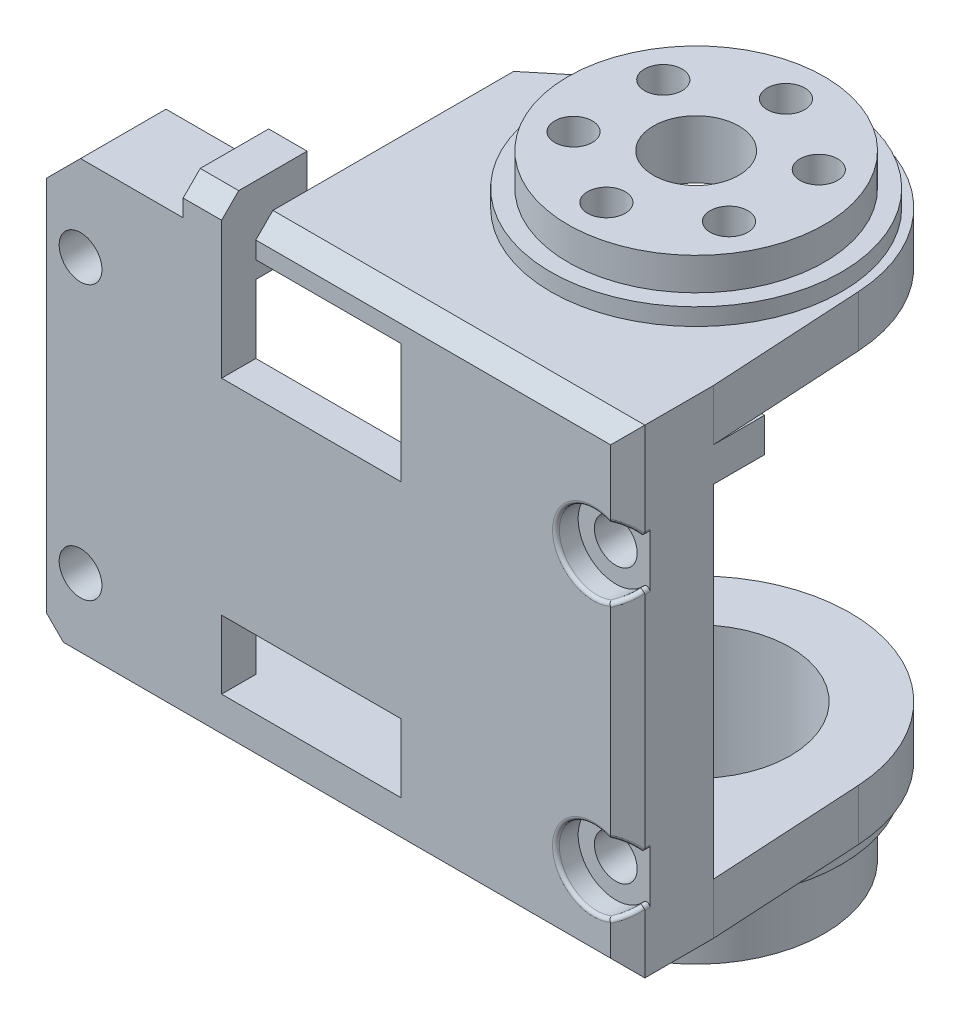
SolidWorks part; units mm, degrees
ref_plane "前视基准面" through (0, 0, 0) normal (0, 0, 1) x (1, 0, 0)
ref_plane "上视基准面" through (0, 0, 0) normal (0, 1, 0) x (1, 0, 0)
ref_plane "右视基准面" through (0, 0, 0) normal (1, 0, 0) x (0, 0, -1)
sketch "草图1" plane through (0, 0, 0) normal (0, 0, 1) x (1, 0, 0)
  line L0 (-26, 14) -> (-26, 12)
  line L1 (0, 14) -> (-34, 14)
  line L2 (0, 14) -> (0, -14)
  line L3 (0, -14) -> (-34, -14)
  line L4 (-34, 14) -> (-34, -14)
  line L5 (-26, 12) -> (-34, 12)
  dimension "D1" = 28
  dimension "D2" = 34
  dimension "D3" = 2
  dimension "D4" = 8
extrude "凸台-拉伸1" add sketch "草图1" against normal blind 2 contours L0 L5 L4 L3 L2 L1 | L5 L0 L1 L4 region at (-16.7778, -0.2222, 0) region at (-30, 13, 0)
sketch "草图2" plane through (0, -14, 0) normal (0, -1, 0) x (1, 0, 0)
  line L0 (-34, 0) -> (-34, -5)
  line L1 (0, 0) -> (-34, 0) construction
  line L2 (-34, 0) -> (0, 0)
  line L3 (0, -2) -> (0, 0) construction
  line L4 (0, 0) -> (0, -5)
  line L5 (-15.2175, -20.4505) -> (-34, -5)
  line L6 (0, -5) -> (-0.5146, -14.0131)
  circle A0 centre (-9.5, -13.5) radius 9
  line M7 (0, 0) -> (-34, 0)
  line M8 (-34, 0) -> (-34, -2)
  line M9 (-34, -2) -> (0, -2)
  line M10 (0, -2) -> (0, 0)
  dimension "D2" = 9.5
  dimension "D3" = 18
  dimension "D1" = 13.5
  dimension "D4" = 5
  dimension "D5" = 5
  dimension "D6" = 34
extrude "凸台-拉伸2" add sketch "草图2" against normal blind 3 contours M10 M7 M8 M9 | A0 L6 L4 L0 L5 M9 | A0 region at (-17, -14, -1) region at (-18.8639, -14, -6.5539) region at (-9.5, -14, -13.5)
ref_axis "基准轴1" through (-9.5, -11, -13.5) along (0, -1, 0)
sketch "草图4" plane through (0, -14, 0) normal (0, -1, 0) x (1, 0, 0)
  circle A0 centre (-9.5, -13.5) radius 7.5
  dimension "D1" = 15
extrude "凸台-拉伸3" add sketch "草图4" along normal blind 5
sketch "草图5" plane through (0, -14, 0) normal (0, -1, 0) x (1, 0, 0)
  circle A2 centre (-9.5, -13.5) radius 8.5
  circle A3 centre (-9.5, -13.5) radius 8.5
  dimension "D1" = 1
extrude "凸台-拉伸4" add sketch "草图5" along normal blind 1
mirror "镜向1" about plane through (0, 0, 0) normal (0, 1, 0) of "凸台-拉伸2", "凸台-拉伸4", "凸台-拉伸3"
sketch "草图6" plane through (0, 19, 0) normal (0, 1, 0) x (1, 0, 0)
  circle A1 centre (-9.5, 13.5) radius 7.5
  circle A2 centre (-9.5, 13.5) radius 7.5
  dimension "D1" = 0
extrude "切除-拉伸1" cut sketch "草图6" against normal blind 2.1
sketch "草图7" plane through (0, 0, -2) normal (0, 0, -1) x (-1, 0, 0)
  line L0 (15.2175, -11) -> (34, -11) construction
  line L1 (13.25, -7) -> (23.75, -7)
  line L2 (13.25, -7) -> (13.25, -11)
  line L3 (13.25, -11) -> (23.75, -11)
  line L4 (23.75, -7) -> (23.75, -11)
  line L5 (34, 11) -> (34, -11) construction
  line L7 (13.25, 12) -> (21.75, 12)
  line L8 (13.25, 12) -> (13.25, 5)
  line L9 (13.25, 5) -> (23.75, 5)
  line L11 (0, 14) -> (34, 14) construction
  line L14 (23.75, 14) -> (21.75, 14)
  line L15 (21.75, 12) -> (21.75, 14)
  line L16 (23.75, 14) -> (23.75, 5)
  dimension "D1" = 10.25
  dimension "D2" = 10.5
  dimension "D3" = 4
  dimension "D4" = 12
  dimension "D5" = 2
  dimension "D6" = 7
extrude "切除-拉伸2" cut sketch "草图7" against normal through all and the other way through all
sketch "草图8" plane through (0, 0, -2) normal (0, 0, -1) x (-1, 0, 0)
  line L0 (0, 11) -> (13.25, 11) construction
  line L1 (0, 11) -> (1.26, 11)
  line L2 (0, 11) -> (0, 9)
  line L3 (0, 9) -> (1.26, 9)
  line L4 (1.26, 11) -> (1.26, 9)
  line L5 (11.99, 11) -> (13.25, 11)
  line L6 (11.99, 11) -> (11.99, 9)
  line L7 (11.99, 9) -> (13.25, 9)
  line L8 (13.25, 11) -> (13.25, 9)
  line L9 (13.25, 5) -> (13.25, 11) construction
  dimension "D1" = 1.26
  dimension "D2" = 2
extrude "凸台-拉伸5" add sketch "草图8" along normal blind 3
sketch "草图9" plane through (0, 0, -5) normal (0, 0, -1) x (-1, 0, 0)
  line L0 (34, 11) -> (34, -11) construction
  line L1 (23.75, 11) -> (34, 11)
  line L2 (23.75, 11) -> (23.75, 9)
  line L3 (23.75, 9) -> (34, 9)
  line L4 (34, 11) -> (34, 9)
  line L5 (13.25, 9) -> (13.25, 11) construction
extrude "凸台-拉伸6" add sketch "草图9" against normal up to surface (3 mm away) up to face at (-15.1562, 2, -2)
sketch "草图10" plane through (0, 0, -5) normal (0, 0, -1) x (-1, 0, 0)
  line L1 (23.75, 9) -> (34, 9)
  line L2 (23.75, 9) -> (23.75, 14)
  line L3 (23.75, 14) -> (34, 14)
  line L4 (34, 9) -> (34, 14)
extrude "切除-拉伸3" cut sketch "草图10" along normal through all
sketch "草图11" plane through (0, 0, -5) normal (0, 0, -1) x (-1, 0, 0)
  line L1 (34, 14) -> (26, 14)
  line L2 (34, 14) -> (34, 12)
  line L3 (34, 12) -> (26, 12)
  line L4 (26, 14) -> (26, 12)
  point P5 (0, 0)
  dimension "D1" = 2
  dimension "D2" = 8
extrude "切除-拉伸4" cut sketch "草图11" against normal through all
sketch "草图21" plane through (0, 0, -5) normal (0, 0, -1) x (-1, 0, 0)
  line L0 (11.99, 11) -> (11.99, 9) construction
  line L1 (11.99, 9) -> (13.25, 9) construction
  line L2 (13.25, 9) -> (13.25, 11) construction
  line L3 (13.25, 11) -> (11.99, 11) construction
  line L4 (0, 11) -> (0, 9) construction
  line L5 (0, 9) -> (1.26, 9) construction
  line L6 (1.26, 9) -> (1.26, 11) construction
  line L7 (1.26, 11) -> (0, 11) construction
  line L8 (11.99, 11) -> (11.99, 9)
  line L9 (11.99, 9) -> (13.25, 9)
  line L10 (13.25, 9) -> (13.25, 11)
  line L11 (13.25, 11) -> (11.99, 11)
  line L12 (0, 11) -> (0, 9)
  line L13 (0, 9) -> (1.26, 9)
  line L14 (1.26, 9) -> (1.26, 11)
  line L15 (1.26, 11) -> (0, 11)
extrude "凸台-拉伸7" add sketch "草图21" along normal blind 3
sketch "草图20" plane through (0, 0, -2) normal (0, 0, -1) x (-1, 0, 0)
  line L0 (9.5, 6) -> (13.25, 6)
  line L1 (0, 0) -> (9.5, 0) construction
  line L2 (9.5, 0) -> (9.5, -1) construction
  line L3 (9.5, -8) -> (13.25, -8)
  line L4 (13.25, -8) -> (13.25, -11)
  line L5 (13.25, -11) -> (0, -11)
  line L6 (0, -11) -> (0, 11)
  line L7 (0, 11) -> (13.25, 11)
  line L8 (13.25, 11) -> (13.25, 6)
  line L9 (1.26, 11) -> (11.99, 11) construction
  line L10 (13.25, 5) -> (13.25, 9) construction
  arc A0 (9.5, 6) -> (9.5, -8) centre (9.5, -1) ccw
  arc A2 (9.5, -8) -> (9.5, 6) centre (9.5, -1) ccw construction
  dimension "D1" = 14
  dimension "D2" = 9.5
  dimension "D3" = 1
extrude "凸台-拉伸8" add sketch "草图20" along normal blind 3
fillet "圆角2" radius 1 2 edges at (-13.25, -8, -3.5) (-13.25, 6, -3.5)
hole_wizard "M2 间隙孔1" positions "草图12" profile "草图13" hole size "M2" standard "GB" end condition through all
sketch "草图12" plane through (0, 0, 0) normal (0, 0, -1) x (-1, 0, 0)
  line L1 (2, 7) -> (32, 7)
  line L2 (2, 7) -> (2, -9)
  line L3 (2, -9) -> (32, -9)
  line L4 (32, 7) -> (32, -9)
  line L5 (23.75, 5) -> (13.25, 5) construction
  line L6 (13.25, -7) -> (23.75, -7) construction
  line L7 (13.25, 5) -> (13.25, 7) construction
  line L8 (23.75, 9) -> (23.75, 5) construction
  point P0 (2, 7)
  point P2 (2, -9)
  point P4 (32, 7)
  point P6 (32, -9)
  dimension "D1" = 2
  dimension "D2" = 2
  dimension "D3" = 11.25
  dimension "D4" = 8.25
sketch "草图13" plane through (-2, 7, 0) normal (1, 0, 0) x (0, -1, 0)
  line L0 (0, 0) -> (0, 22.5)
  line L1 (0, 22.5) -> (1.25, 22.5)
  line L2 (1.25, 22.5) -> (1.25, 0)
  line L5 (1.25, 0) -> (0, 0)
  line L11 (0, -6.35) -> (0, 107.95) construction
  dimension "通孔孔直径" = 2.5
  dimension "通孔孔深度" = 22.5
chamfer "倒角1" distance 1 angle 45 4 edges at (-24.875, 14, 0) (-10.875, 14, 0) (-17, -14, 0) (0, 0, 0)
chamfer "倒角2" distance 2 angle 45 2 edges at (-34, -14, -3) (-34, 12, -2.5)
sketch "草图14" plane through (0, -19, 0) normal (0, -1, 0) x (1, 0, 0)
  circle A2 centre (-9.5, -13.5) radius 5.5
  circle A3 centre (-9.5, -13.5) radius 5.5
  dimension "D1" = 2
extrude "切除-拉伸5" cut sketch "草图14" against normal up to next
sketch "草图15" plane through (0, 16.9, 0) normal (0, 1, 0) x (1, 0, 0)
  circle A2 centre (-9.5, 13.5) radius 2.5
  circle A3 centre (-9.5, 13.5) radius 2.5
  dimension "D1" = 5
extrude "切除-拉伸6" cut sketch "草图15" against normal up to next
hole_wizard "M2 六角圆柱头螺钉的柱形沉头孔1" positions "草图16" profile "草图18" counterbore size "M2" standard "GB" end condition through all
sketch "草图16" plane through (0, 11, 0) normal (0, -1, 0) x (-1, 0, 0)
  line L0 (9.5, 18.75) -> (9.5, 13.5) construction
  circle A0 centre (9.5, 13.5) radius 2.5 construction
  point P0 (9.5, 18.75)
  dimension "D1" = 5.25
sketch "草图18" plane through (-9.5, 11, -18.75) normal (1, 0, 0) x (0, 0, -1)
  line L0 (0, 0) -> (0, 5.9)
  line L1 (0, 5.9) -> (1.1, 5.9)
  line L3 (1.1, 5.9) -> (1.1, 2.5)
  line L4 (1.1, 2.5) -> (2.2, 2.5)
  line L5 (2.2, 2.5) -> (2.2, 0)
  line L7 (2.2, 0) -> (0, 0)
  line L11 (0, -6.35) -> (0, 107.95) construction
  dimension "通孔孔直径" = 2.2
  dimension "通孔孔深度" = 5.9
  dimension "柱形沉头孔直径" = 4.4
  dimension "柱形沉头孔深度" = 2.5
pattern_circular "阵列(圆周)1" count 6 over 360 about axis through (-9.5, -19.001, -13.5) along (0, 1, 0) of "M2 六角圆柱头螺钉的柱形沉头孔1"
sketch "草图19" plane through (0, 11, 0) normal (0, -1, 0) x (1, 0, 0)
  line L0 (-4.9534, -10.875) -> (-4.9534, -16.125)
  line L1 (-5, -10.9019) -> (-9.5, -8.3038)
  line L2 (-9.5, -8.3038) -> (-14, -10.9019)
  line L3 (-14, -10.9019) -> (-14, -16.0981)
  line L4 (-14, -16.0981) -> (-9.5, -18.6962)
  line L5 (-9.5, -18.6962) -> (-5, -16.0981)
  line L6 (-5, -16.0981) -> (-5, -10.9019)
  circle A0 centre (-9.5, -13.5) radius 4.5 construction
  dimension "D1" = 9
extrude "切除-拉伸7" cut sketch "草图19" against normal up to surface (2.5 mm away) contours L3 L4 L5 L6 L1 L2 up to face at (-14.0466, 13.5, -11.975)
fillet "圆角1" radius 0.4 12 edges at (-12.1185, 12.25, -17.1844) (-14, 12.75, -13.9255) (-14, 12.75, -13.0745) (-7.6185, 12.25, -9.3901) (-6.8815, 12.25, -9.8156) (-5, 12.25, -13.0745) (-5, 12.25, -13.9255) (-6.8815, 12.25, -17.1844) (-7.6185, 12.25, -17.6099) (-11.3815, 12.25, -17.6099) (-11.3815, 12.25, -9.3901) (-12.1185, 12.25, -9.8156)
sketch "草图22" plane through (0, 0, 0) normal (0, 0, 1) x (1, 0, 0)
  circle A0 centre (-2, 7) radius 2.2
  circle A1 centre (-2, -9) radius 2.2
  dimension "D1" = 4.4
  dimension "D2" = 4.4
extrude "切除-拉伸8" cut sketch "草图22" against normal blind 1.3
fillet "圆角3" radius 0.2 10 edges at (0, -9.9165, -1.15) (-0.4119, -10.5225, -0.5881) (-0.4119, -7.4775, -0.5881) (-4.2, -9, 0) (0, -8.0835, -1.15) (0, 7.9165, -1.15) (0, 6.0835, -1.15) (-0.4119, 5.4775, -0.5881) (-4.2, 7, 0) (-0.4119, 8.5225, -0.5881)
